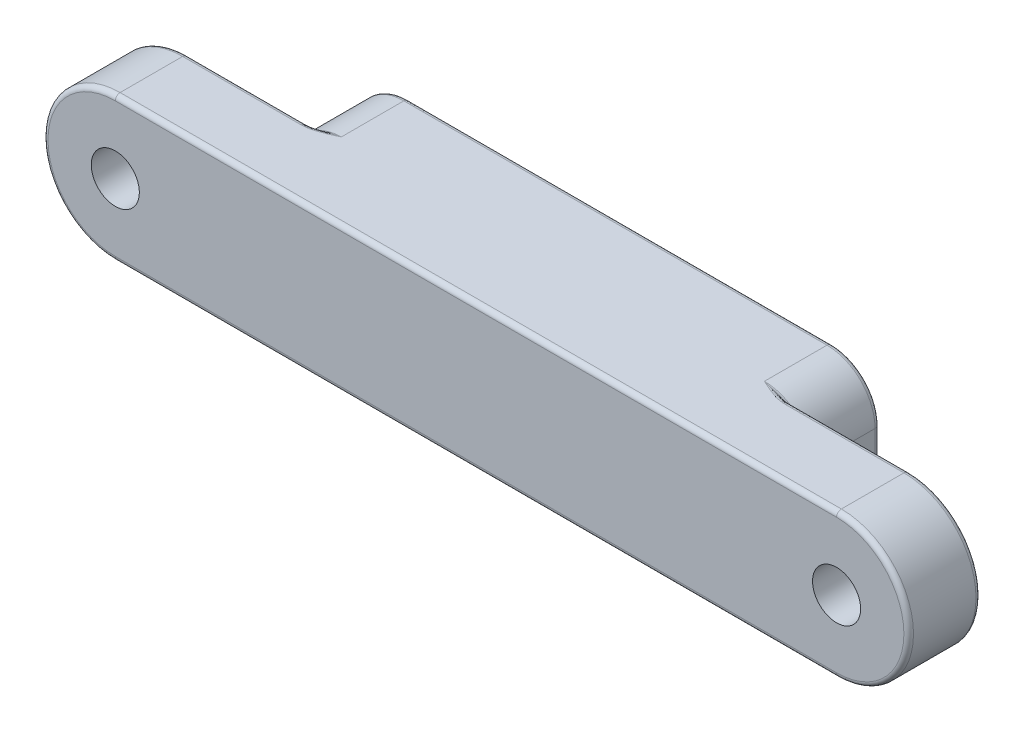
SolidWorks part; units mm, degrees
material "Malleable Cast Iron"
ref_plane "Front Plane" through (0, 0, 0) normal (0, 0, 1) x (1, 0, 0)
ref_plane "Top Plane" through (0, 0, 0) normal (0, 1, 0) x (1, 0, 0)
ref_plane "Right Plane" through (0, 0, 0) normal (1, 0, 0) x (0, 0, -1)
sketch "Sketch1" plane through (0, 0, 0) normal (0, 0, 1) x (1, 0, 0)
  line L1 (-150, -30) -> (150, -30)
  line L3 (-150, 30) -> (150, 30)
  line L5 (-150, -30) -> (150, 30) construction
  line L6 (-150, 30) -> (150, -30) construction
  arc A0 (-150, 30) -> (-150, -30) centre (-150, 0) ccw
  arc A1 (150, -30) -> (150, 30) centre (150, 0) ccw
  circle A2 centre (-150, 0) radius 10
  circle A3 centre (150, 0) radius 10
  point P0 (0, 0)
  dimension "D1" = 20
  dimension "D2" = 20
  dimension "D3" = 30
  dimension "D4" = 300
extrude "Boss-Extrude1" add sketch "Sketch1" along normal blind 60
sketch "Sketch2" plane through (0, 0, 0) normal (0, 0, 1) x (1, 0, 0)
  line L1 (150, 30) -> (-150, 30) construction
  line L6 (108, 30) -> (150, 30)
  line L7 (150, -30) -> (108, -30)
  line L8 (-108, 30) -> (-150, 30)
  line L9 (-108, -30) -> (-150, -30)
  line L14 (-108, -30) -> (-108, 30)
  line L18 (108, -30) -> (108, 30)
  arc A0 (150, -30) -> (150, 30) centre (150, 0) ccw
  arc A1 (-150, 30) -> (-150, -30) centre (-150, 0) ccw
  dimension "D1" = 42
  dimension "D2" = 42
extrude "Cut-Extrude2" cut sketch "Sketch2" along normal blind 30 contours L7 A0 L6 | L8 A1 L9 region at (141.1229, 0, 0) region at (-141.1229, 0, 0)
fillet "Fillet1" radius 20 4 edges at (108, -30, 15) (108, 30, 15) (-108, 30, 15) (-108, -30, 15)
fillet "Fillet2" radius 2 24 edges at (-180, 0, 60) (0, 30, 60) (180, 0, 60) (119, -30, 30) (180, 0, 30) (102.1421, -24.1421, 30) (102.1421, 24.1421, 30) (-102.1421, -24.1421, 30) (-102.1421, 24.1421, 30) (-119, -30, 30) (-180, 0, 30) (102.1421, 24.1421, 0) (0, 30, 0) (-102.1421, 24.1421, 0) (-108, 0, 0) (-102.1421, -24.1421, 0) (0, -30, 0) (102.1421, -24.1421, 0) (108, 0, 0) (0, -30, 60) (119, 30, 30) (108, 0, 30) (-108, 0, 30) (-119, 30, 30)
